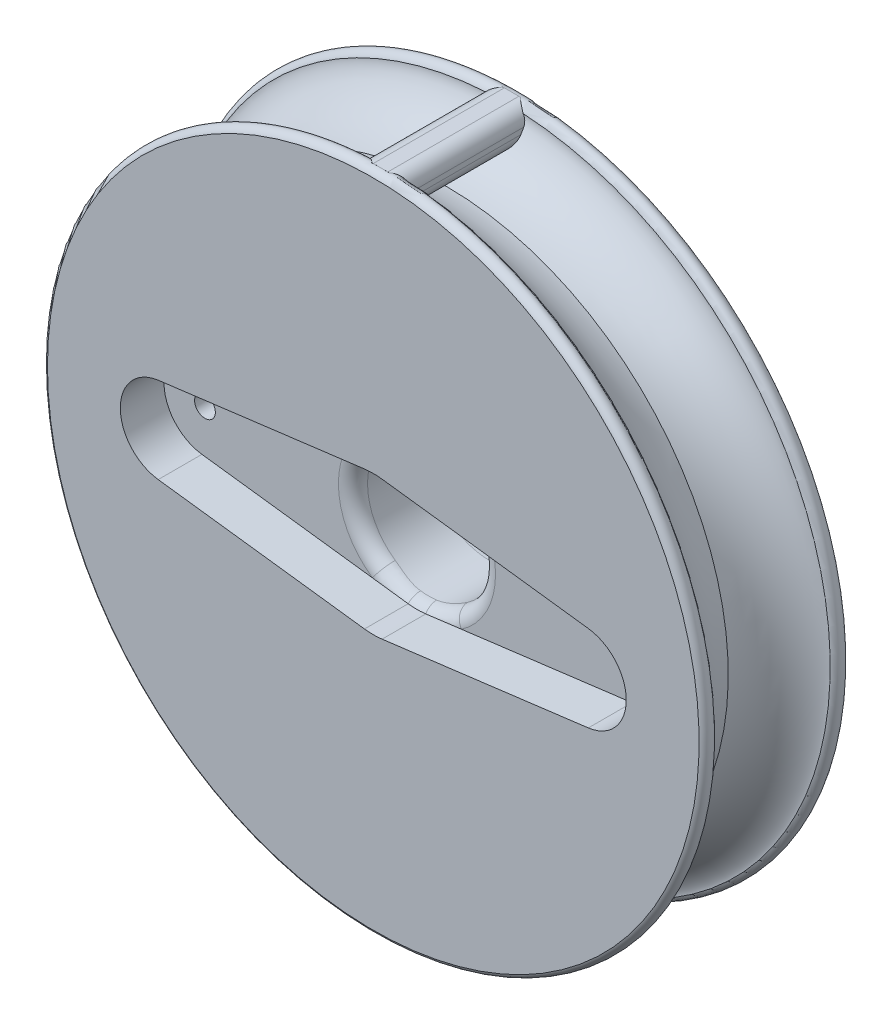
SolidWorks part; units mm, degrees
ref_plane "Front Plane" through (0, 0, 0) normal (0, 0, 1) x (1, 0, 0)
ref_plane "Top Plane" through (0, 0, 0) normal (0, 1, 0) x (1, 0, 0)
ref_plane "Right Plane" through (0, 0, 0) normal (1, 0, 0) x (0, 0, -1)
sketch "Sketch1" plane through (0, 0, 0) normal (0, 0, 1) x (1, 0, 0)
  line L4 (0.6051, -4.7559) -> (14.765, -2.9543)
  line L5 (14.765, 2.9543) -> (0.6051, 4.7559)
  line L6 (-0.6051, 4.7559) -> (-14.765, 2.9543)
  line L7 (-14.765, -2.9543) -> (-0.6051, -4.7559)
  line L8 (0.6051, -4.7559) -> (14.765, -2.9543)
  line L9 (14.765, 2.9543) -> (0.6051, 4.7559)
  line L10 (-0.6051, 4.7559) -> (-14.765, 2.9543)
  line L11 (-14.765, -2.9543) -> (-0.6051, -4.7559)
  arc A4 (14.765, -2.9543) -> (14.765, 2.9543) centre (14.3891, 0) ccw
  arc A5 (0.6051, 4.7559) -> (-0.6051, 4.7559) centre (0, 0) ccw
  arc A6 (-14.765, 2.9543) -> (-14.765, -2.9543) centre (-14.3891, 0) ccw
  arc A7 (-0.6051, -4.7559) -> (0.6051, -4.7559) centre (0, 0) ccw
  arc A8 (14.765, -2.9543) -> (14.765, 2.9543) centre (14.3891, 0) ccw
  arc A9 (0.6051, 4.7559) -> (-0.6051, 4.7559) centre (0, 0) ccw
  arc A10 (-14.765, 2.9543) -> (-14.765, -2.9543) centre (-14.3891, 0) ccw
  arc A11 (-0.6051, -4.7559) -> (0.6051, -4.7559) centre (0, 0) ccw
  dimension "D1" = 0
extrude "Extrude-Thin1" add sketch "Sketch1" against normal blind 3 thin thin type one direction wall 2
sketch "Sketch2" plane through (0, 0, -3) normal (0, 0, -1) x (-1, 0, 0)
  line L0 (-0.8575, -6.7399) -> (-15.0174, -4.9383) construction
  line L1 (-15.0174, 4.9383) -> (-0.8575, 6.7399) construction
  line L2 (0.8575, 6.7399) -> (15.0174, 4.9383) construction
  line L3 (15.0174, -4.9383) -> (0.8575, -6.7399) construction
  line L4 (-0.8575, -6.7399) -> (-15.0174, -4.9383)
  line L5 (-15.0174, 4.9383) -> (-0.8575, 6.7399)
  line L6 (0.8575, 6.7399) -> (15.0174, 4.9383)
  line L7 (15.0174, -4.9383) -> (0.8575, -6.7399)
  arc A0 (-0.8575, -6.7399) -> (0.8575, -6.7399) centre (0, 0) ccw construction
  arc A1 (-15.0174, 4.9383) -> (-15.0174, -4.9383) centre (-14.3891, 0) ccw construction
  arc A2 (0.8575, 6.7399) -> (-0.8575, 6.7399) centre (0, 0) ccw construction
  arc A3 (15.0174, -4.9383) -> (15.0174, 4.9383) centre (14.3891, 0) ccw construction
  arc A4 (-0.8575, -6.7399) -> (0.8575, -6.7399) centre (0, 0) ccw
  arc A5 (-15.0174, 4.9383) -> (-15.0174, -4.9383) centre (-14.3891, 0) ccw
  arc A6 (0.8575, 6.7399) -> (-0.8575, 6.7399) centre (0, 0) ccw
  arc A7 (15.0174, -4.9383) -> (15.0174, 4.9383) centre (14.3891, 0) ccw
extrude "Boss-Extrude1" add sketch "Sketch2" along normal blind 2
sketch "Sketch3" plane through (0, 0, -5) normal (0, 0, -1) x (-1, 0, 0)
  circle A0 centre (0, 0) radius 19.37
  dimension "D1" = 38.74
extrude "Boss-Extrude2" add sketch "Sketch3" along normal blind 5
sketch "Sketch5" plane through (0, 0, -3) normal (0, 0, 1) x (1, 0, 0)
  line L4 (-14.765, -2.9543) -> (-0.6051, -4.7559)
  line L5 (0.6051, -4.7559) -> (14.765, -2.9543)
  line L6 (14.765, 2.9543) -> (0.6051, 4.7559)
  line L7 (-0.6051, 4.7559) -> (-14.765, 2.9543)
  line L8 (-14.765, -2.9543) -> (-0.6051, -4.7559)
  line L9 (0.6051, -4.7559) -> (14.765, -2.9543)
  line L10 (14.765, 2.9543) -> (0.6051, 4.7559)
  line L11 (-0.6051, 4.7559) -> (-14.765, 2.9543)
  circle A0 centre (-14.5542, 0) radius 0.7112
  circle A1 centre (14.5542, 0) radius 0.7112
  circle A2 centre (0, 0) radius 4.3942
  arc A4 (-14.765, 2.9543) -> (-14.765, -2.9543) centre (-14.3891, 0) ccw
  arc A5 (-0.6051, -4.7559) -> (0.6051, -4.7559) centre (0, 0) ccw
  arc A6 (14.765, -2.9543) -> (14.765, 2.9543) centre (14.3891, 0) ccw
  arc A7 (0.6051, 4.7559) -> (-0.6051, 4.7559) centre (0, 0) ccw
  arc A8 (-14.765, 2.9543) -> (-14.765, -2.9543) centre (-14.3891, 0) ccw
  arc A9 (-0.6051, -4.7559) -> (0.6051, -4.7559) centre (0, 0) ccw
  arc A10 (14.765, -2.9543) -> (14.765, 2.9543) centre (14.3891, 0) ccw
  arc A11 (0.6051, 4.7559) -> (-0.6051, 4.7559) centre (0, 0) ccw
  dimension "D1" = 0
sketch "Sketch6" plane through (0, 0, -5) normal (0, 0, 1) x (1, 0, 0)
  line L4 (-15.0174, -4.9383) -> (-0.8575, -6.7399) construction
  line L5 (0.8575, -6.7399) -> (15.0174, -4.9383) construction
  line L6 (15.0174, 4.9383) -> (0.8575, 6.7399) construction
  line L7 (-0.8575, 6.7399) -> (-15.0174, 4.9383) construction
  line L8 (-15.0174, -4.9383) -> (-0.8575, -6.7399)
  line L9 (0.8575, -6.7399) -> (15.0174, -4.9383)
  line L10 (15.0174, 4.9383) -> (0.8575, 6.7399)
  line L11 (-0.8575, 6.7399) -> (-15.0174, 4.9383)
  arc A10 (-15.0174, 4.9383) -> (-15.0174, -4.9383) centre (-14.3891, 0) ccw construction
  arc A11 (-0.8575, -6.7399) -> (0.8575, -6.7399) centre (0, 0) ccw construction
  arc A12 (15.0174, -4.9383) -> (15.0174, 4.9383) centre (14.3891, 0) ccw construction
  arc A13 (0.8575, 6.7399) -> (-0.8575, 6.7399) centre (0, 0) ccw construction
  arc A14 (-15.0174, 4.9383) -> (-15.0174, -4.9383) centre (-14.3891, 0) ccw
  arc A15 (-0.8575, -6.7399) -> (0.8575, -6.7399) centre (0, 0) ccw
  arc A16 (15.0174, -4.9383) -> (15.0174, 4.9383) centre (14.3891, 0) ccw
  arc A17 (0.8575, 6.7399) -> (-0.8575, 6.7399) centre (0, 0) ccw
  circle A18 centre (0, 0) radius 19.37 construction
  circle A19 centre (0, 0) radius 19.37
  circle M2 centre (0, 0) radius 19.37
  arc M3 (-15.0174, -4.9383) -> (-15.0174, 4.9383) centre (-14.3891, 0) cw
  line M4 (-15.0174, 4.9383) -> (-0.8575, 6.7399)
  arc M5 (-0.8575, 6.7399) -> (0.8575, 6.7399) centre (0, 0) cw
  line M6 (0.8575, 6.7399) -> (15.0174, 4.9383)
  arc M7 (15.0174, 4.9383) -> (15.0174, -4.9383) centre (14.3891, 0) cw
extrude "Boss-Extrude3" add sketch "Sketch6" along normal up to surface (5 mm away) contours M7 M2 M3 M4 M5 M6 region at (-8.0066, -6.3826, -5) up to face at (0, 0, 0)
ref_plane "Plane1" through (0, 0, -5) normal (0, 0, 1) x (1, 0, 0)
sketch "Sketch8" plane through (0, 0, 0) normal (1, 0, 0) x (0, 0, -1)
  line L1 (0, 19.37) -> (0, 22.37)
  line L3 (10, 19.37) -> (0, 19.37) construction
  line L4 (10, 19.37) -> (0, 19.37)
  line L5 (5, 21.307) -> (5, -21.307) construction
  line L6 (10, 19.37) -> (10, 22.37)
  arc A0 (0, 22.37) -> (1, 22.37) centre (0.5, 22.1863) cw
  arc A1 (10, 22.37) -> (9, 22.37) centre (9.5, 22.1863) ccw
  spline S0 degree 3 poles (1, 22.37) (1.0131, 21.6591) (2.153, 19.7355) (5, 19.37) knots 0 0 0 0 1 1 1 1
  spline S1 degree 3 poles (9, 22.37) (8.9869, 21.6591) (7.847, 19.7355) (5, 19.37) knots 0 0 0 0 1 1 1 1
  dimension "D3" = 0.5327
  dimension "D1" = 3
  dimension "D2" = 1
revolve "Revolve1" add sketch "Sketch8" angle 360 about axis through (0, 0, -10) along (0, 0, 1) region at (0, 20.5517, -8.7281) region at (0, 20.5517, -1.2719)
sketch "Sketch9" plane through (0, 0, -3) normal (0, 0, 1) x (1, 0, 0)
  circle A0 centre (14.5542, 0) radius 0.7112 construction
  circle A1 centre (0, 0) radius 4.3942 construction
  circle A2 centre (-14.5542, 0) radius 0.7112 construction
  circle A3 centre (14.5542, 0) radius 0.7112
  circle A4 centre (0, 0) radius 4.3942
  circle A5 centre (-14.5542, 0) radius 0.7112
extrude "Cut-Extrude1" cut sketch "Sketch9" against normal through all both and the other way through all
fillet "Fillet1" radius 1 1 edges at (-4.3942, 0, -3)
fillet "Fillet2" radius 2 1 edges at (4.3942, 0, -10)
sketch "Sketch10" plane through (0, 0, 0) normal (1, 0, 0) x (0, 0, -1)
  line L0 (0.5, 22.719) -> (9.5, 22.719)
  line L1 (2.3782, 20.37) -> (7.6218, 20.37)
  line L2 (5, 22.719) -> (5, 20.37) construction
  arc A0 (1, 22.37) -> (0, 22.37) centre (0.5, 22.1863) ccw construction
  arc A1 (10, 22.37) -> (9, 22.37) centre (9.5, 22.1863) ccw construction
  arc A2 (2.3782, 20.37) -> (0.5, 22.719) centre (3.2721, 23.0101) cw
  arc A3 (7.6218, 20.37) -> (9.5, 22.719) centre (6.7279, 23.0101) ccw
  circle A4 centre (5, 21.5445) radius 0.005
  spline S0 degree 3 poles (5, 19.37) (2.153, 19.7355) (1.0131, 21.6591) (1, 22.37) knots 0 0 0 0 1 1 1 1 construction
  spline S1 degree 3 poles (9, 22.37) (8.9869, 21.6591) (7.847, 19.7355) (5, 19.37) knots 0 0 0 0 1 1 1 1 construction
  point P23 (5, 21.5445)
  dimension "D2" = 0.01
  dimension "D1" = 1
extrude "Boss-Extrude4" add sketch "Sketch10" along normal blind 1.5 and the other way blind 1.5
fillet "Fillet3" radius 1 2 edges at (-1.5, 20.37, -5) (1.5, 20.37, -5)
fillet "Fillet4" radius 1 2 edges at (1.5, 22.719, -5) (-1.5, 22.719, -5)
